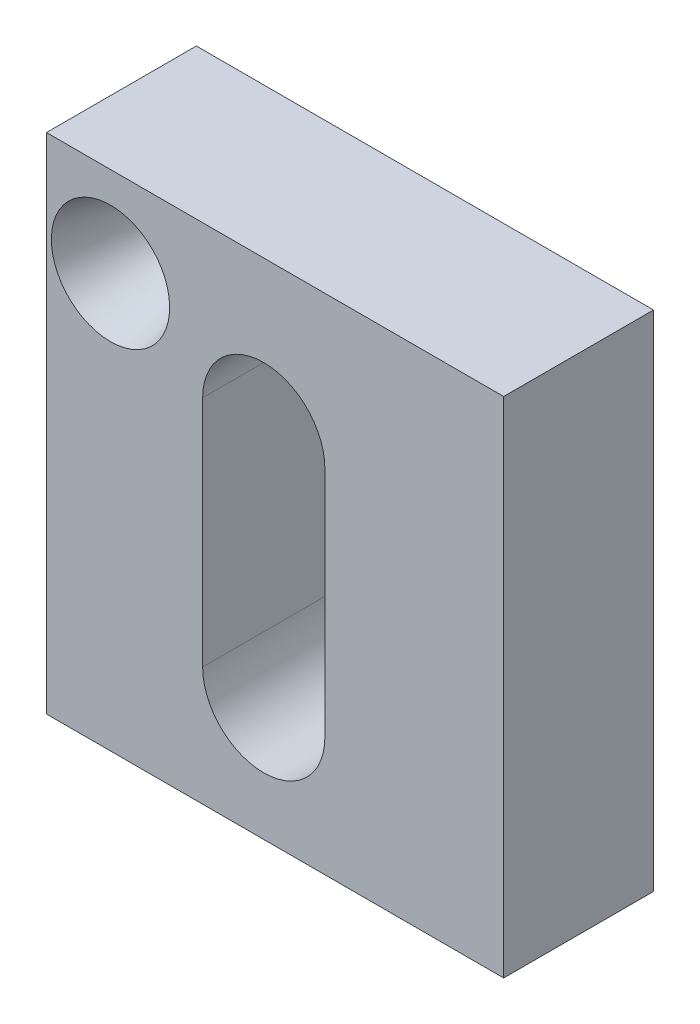
SolidWorks part; units mm, degrees
ref_plane "Front Plane" through (0, 0, 0) normal (0, 0, 1) x (1, 0, 0)
ref_plane "Top Plane" through (0, 0, 0) normal (0, 1, 0) x (1, 0, 0)
ref_plane "Right Plane" through (0, 0, 0) normal (1, 0, 0) x (0, 0, -1)
sketch "Sketch1" plane through (0, 0, 0) normal (0, 0, 1) x (1, 0, 0)
  line L0 (-14.001, 0) -> (24.7415, 0)
  line L1 (24.7415, 0) -> (24.7415, 42.6744)
  line L2 (24.7415, 42.6744) -> (-14.001, 42.6744)
  line L3 (-14.001, 42.6744) -> (-14.001, 0)
  line L4 (4.4113, 29.8241) -> (4.4113, 10.0692) construction
  line L5 (9.5897, 29.8241) -> (9.5897, 10.0692)
  line L6 (-0.7672, 29.8241) -> (-0.7672, 10.0692)
  arc A0 (9.5897, 29.8241) -> (-0.7672, 29.8241) centre (4.4113, 29.8241) ccw
  arc A1 (-0.7672, 10.0692) -> (9.5897, 10.0692) centre (4.4113, 10.0692) ccw
  point P7 (4.4113, 19.9467)
extrude "Boss-Extrude1" add sketch "Sketch1" along normal blind 12.7 contours L3 L0 L1 L2 | L6 A1 L5 A0
sketch "Sketch3" plane through (24.7415, 0, 0) normal (1, 0, 0) x (0, 0, -1)
  circle A0 centre (-8.4771, 21.3372) radius 5.4571
sketch "Sketch4" plane through (-14.001, 0, 0) normal (-1, 0, 0) x (0, 0, 1)
  circle A0 centre (8.4771, 21.3372) radius 2.1177
ref_plane "Plane1" through (0, 0, 6.35) normal (0, 0, -1) x (-1, 0, 0)
sketch "Sketch5" plane through (0, 0, 6.35) normal (0, 0, -1) x (-1, 0, 0)
  line L0 (-24.7415, 21.3372) -> (14.001, 21.3372)
  line L1 (-24.7415, 26.7943) -> (-24.7415, 15.8801) construction
  line L2 (14.001, 19.2195) -> (14.001, 23.4549) construction
sketch "Sketch6" plane through (0, 0, 12.7) normal (0, 0, 1) x (1, 0, 0)
  circle A0 centre (-8.5735, 35.0518) radius 5.0104
sketch "Sketch7" plane through (0, 0, 0) normal (0, 0, -1) x (-1, 0, 0)
  circle A0 centre (8.5735, 35.0518) radius 2.2151
loft "Cut-Loft1" cut profiles "Sketch7", "Sketch6" connector at (-6.3887, 35.4176, 0) connector at (-4.5686, 38.0627, 12.7)
